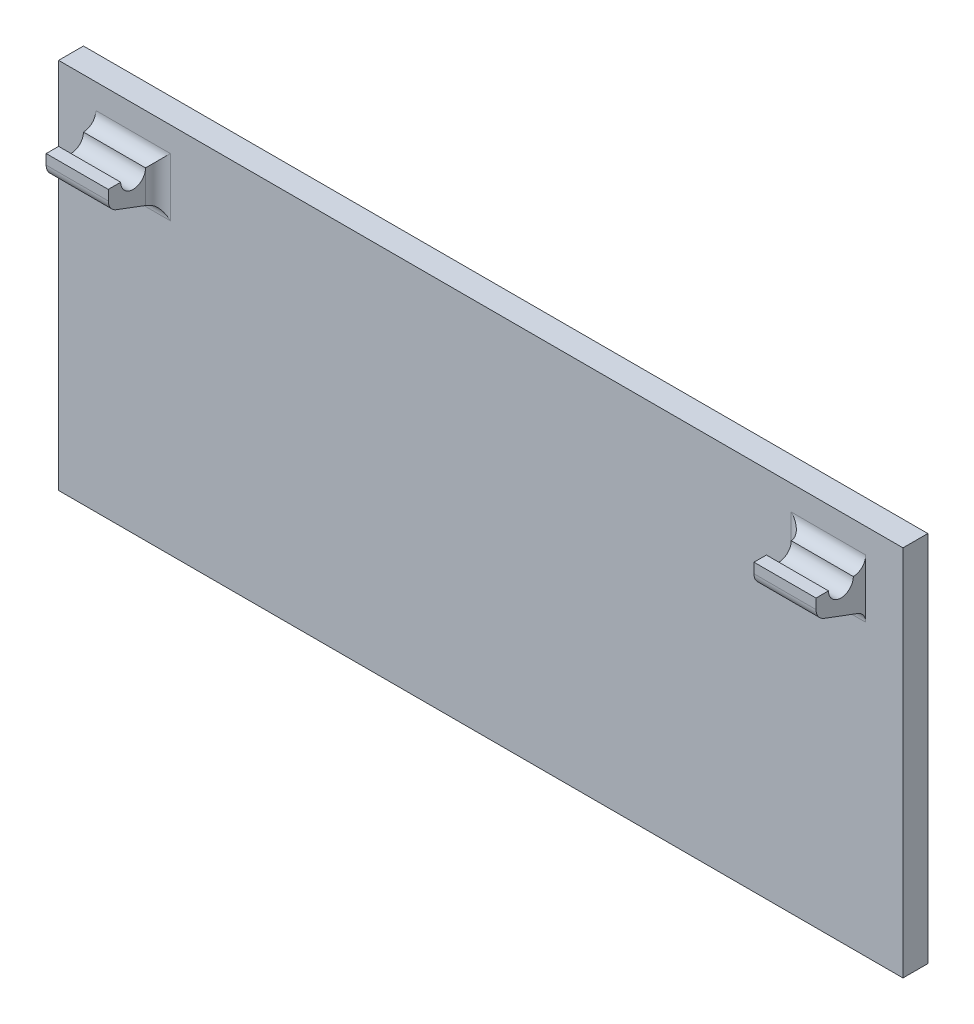
SolidWorks part; units mm, degrees
material "AISI 4340 Steel, annealed"
ref_plane "Front Plane" through (0, 0, 0) normal (0, 0, 1) x (1, 0, 0)
ref_plane "Top Plane" through (0, 0, 0) normal (0, 1, 0) x (1, 0, 0)
ref_plane "Right Plane" through (0, 0, 0) normal (1, 0, 0) x (0, 0, -1)
sketch "Sketch1" plane through (0, 0, 0) normal (0, 0, 1) x (1, 0, 0)
  line L1 (-170, 75) -> (170, 75)
  line L2 (-170, 75) -> (-170, -75)
  line L3 (-170, -75) -> (170, -75)
  line L4 (170, 75) -> (170, -75)
  line L5 (-170, 75) -> (170, -75) construction
  line L6 (-170, -75) -> (170, 75) construction
  point P0 (0, 0)
  dimension "D1" = 340
  dimension "D2" = 150
extrude "Vertical portion" add sketch "Sketch1" along normal blind 10
ref_plane "Plane1" through (155, 0, 0) normal (1, 0, 0) x (0, 0, -1)
sketch "Sketch4" plane through (155, 0, 0) normal (1, 0, 0) x (0, 0, -1)
  line L0 (-10, 75) -> (0, 75) construction
  line L1 (-10, 45) -> (-30, 52.5)
  line L2 (-15, 60) -> (-10, 60)
  line L3 (-10, -75) -> (-10, 75) construction
  line L4 (-10, 60) -> (-10, 55)
  line L5 (-10, 55) -> (-10, 45)
  line L6 (-10, 45) -> (-30, 45) construction
  line L7 (-30, 52.5) -> (-30, 60)
  line L8 (-30, 60) -> (-25, 60)
  line L9 (-30, 52.5) -> (-30, 45) construction
  line L10 (-10, -75) -> (-10, 75) construction
  arc A0 (-25, 60) -> (-15, 60) centre (-20, 60) ccw
  dimension "D1" = 10
  dimension "D6" = 15
  dimension "D2" = 10
  dimension "D3" = 10
  dimension "D4" = 5
  dimension "D5" = 20
extrude "Shaft adapter right" add sketch "Sketch4" against normal blind 25 contours L7 L8 A0 L2 L4 L5 L1
mirror "Shaft adapter left" about plane through (0, 0, 0) normal (1, 0, 0) of "Shaft adapter right"
fillet "Shaft adapter fillets" radius 5 8 edges at (-142.5, 52.5, 30) (142.5, 52.5, 30) (130, 52.5, 10) (-130, 52.5, 10) (-142.5, 45, 10) (142.5, 45, 10) (142.5, 60, 10) (-142.5, 60, 10)
sketch "Sketch5" plane through (0, 0, 0) normal (0, 0, -1) x (-1, 0, 0)
  line L0 (170, -75) -> (-170, -75) construction
  line L1 (-150, -75) -> (-50, -75)
  line L2 (-150, -75) -> (-150, -70)
  line L3 (-150, -70) -> (-50, -70)
  line L4 (-50, -75) -> (-50, -70)
  line L5 (0, 16.5) -> (0, -16.5) construction
  line L10 (50, -75) -> (50, -70)
  line L11 (150, -70) -> (50, -70)
  line L12 (150, -75) -> (150, -70)
  line L13 (150, -75) -> (50, -75)
  dimension "D1" = 50
  dimension "D2" = 100
  dimension "D3" = 5
extrude "Limit tab (prevents gate from getting pushed out of slot)" add sketch "Sketch5" along normal blind 10
fillet "Limit tab fillets" radius 5 6 edges at (-50, -72.5, 0) (-100, -70, 0) (-150, -72.5, 0) (50, -72.5, 0) (150, -72.5, 0) (100, -70, 0)
